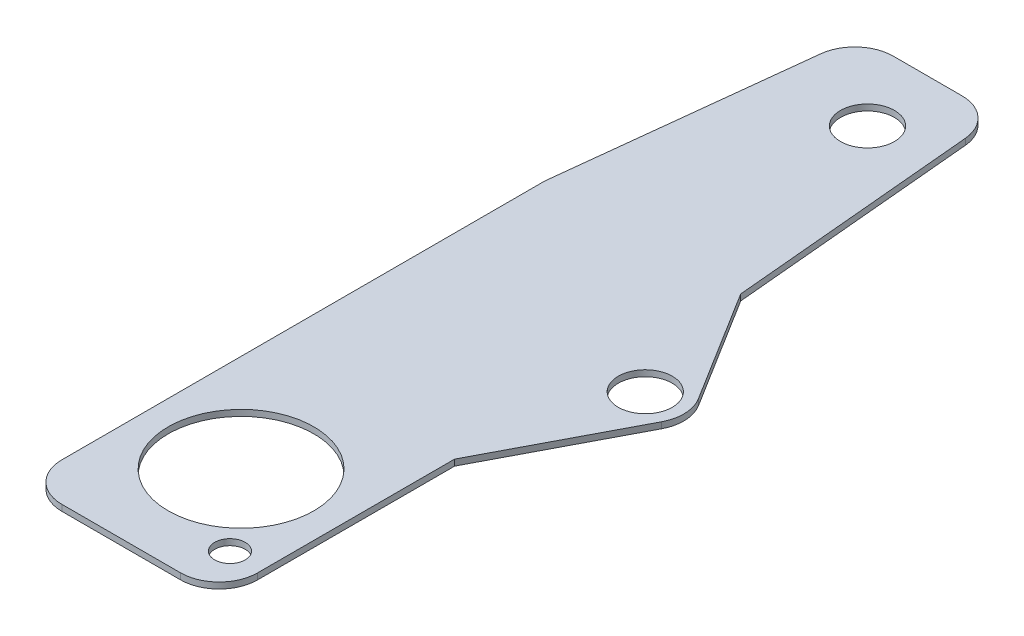
SolidWorks part; units mm, degrees
ref_plane "Front" through (0, 0, 0) normal (0, 0, 1) x (1, 0, 0)
ref_plane "Top" through (0, 0, 0) normal (0, 1, 0) x (1, 0, 0)
ref_plane "Right" through (0, 0, 0) normal (1, 0, 0) x (0, 0, -1)
sketch "Sketch1" plane through (0, 0, 0) normal (0, 1, 0) x (1, 0, 0)
  line L0 (10.4543, 228.6) -> (0, 135.3627)
  line L1 (0, 0) -> (50.8, 0)
  line L2 (0, 0) -> (0, 228.6)
  line L3 (0, 228.6) -> (50.8, 228.6)
  line L4 (50.8, 0) -> (50.8, 228.6)
  line L5 (42.3273, 228.6) -> (50.8, 135.3627)
  line L8 (50.8, 0) -> (24.327, 0)
  line L9 (50.8, 0) -> (50.8, -15)
  line L10 (50.8, -15) -> (24.327, -15)
  line L11 (24.327, 0) -> (24.327, -15)
  line L16 (50.8, 120.6192) -> (50.8, 104.4882)
  line L18 (50.8, 64.8791) -> (50.8, 87.4235)
  circle A2 centre (24.327, 25.5092) radius 5.969
  circle A3 centre (42.3273, 11.2956) radius 3.9601
  circle A12 centre (60.4, 101.001) radius 10
  circle A13 centre (29.5042, 189.5572) radius 7
  circle A14 centre (25.2716, 31.2259) radius 18.9
  dimension "D3" = 20
  dimension "D4" = 11.938
  dimension "D5" = 15
  dimension "D6" = 14
  dimension "D1" = 50.8
  dimension "D2" = 228.6
extrude "Boss-Extrude1" add sketch "Sketch1" along normal blind 1.5875 contours L1 L4 L3 L0 L2 region at (25.443, 0, -115.715)
sketch "Sketch4" plane through (0, 0, -228.6) normal (0, 0, -1) x (-1, 0, 0)
  line L1 (-61.3109, 11.9192) -> (4.9615, 11.9192)
  line L2 (-61.3109, 11.9192) -> (-61.3109, -15.8811)
  line L3 (-61.3109, -15.8811) -> (4.9615, -15.8811)
  line L4 (4.9615, 11.9192) -> (4.9615, -15.8811)
extrude "Cut-Extrude2" cut sketch "Sketch4" against normal blind 20
fillet "Fillet3" radius 10 1 edges at (44.1447, 0.7937, -208.6)
fillet "Fillet4" radius 10 3 edges at (50.8, 0.7937, 0) (0, 0.7937, 0) (8.2118, 0.7937, -208.6)
sketch "Sketch6" plane through (0, 1.5875, 0) normal (0, 1, 0) x (1, 0, 0)
  line L0 (68.8909, 106.2834) -> (50.8, 135.3627)
  line L1 (50.8, 135.3627) -> (50.8, 103.801)
  line L2 (69.2582, 96.3607) -> (50.8, 61.1242)
  line L3 (50.8, 10) -> (50.8, 98.201) construction
  line L4 (50.8, 61.1242) -> (50.8, 96.3607)
  line L5 (50.8, 96.3607) -> (50.8, 98.201)
  circle A0 centre (60.4, 101.001) radius 10
  line M4 (50.8, 10) -> (50.8, 98.201)
  arc M5 (50.8, 98.201) -> (50.8, 103.801) centre (60.4, 101.001) cw
  line M6 (50.8, 103.801) -> (50.8, 135.3627)
extrude "Boss-Extrude3" add sketch "Sketch6" against normal blind 1.5875 contours A0 L0 M6 | A0 M5 | A0 L2 M4 region at (55.8248, 1.5875, -118.0301) region at (60.4, 1.5875, -101.001) region at (56.0341, 1.5875, -82.1407)
sketch "Sketch7" plane through (0, 1.5875, 0) normal (0, 1, 0) x (1, 0, 0)
  circle A0 centre (60.4, 101.001) radius 7
  dimension "D1" = 14
extrude "Cut-Extrude3" cut sketch "Sketch7" against normal blind 1.5875
equation "\"7i\"=101.6"
